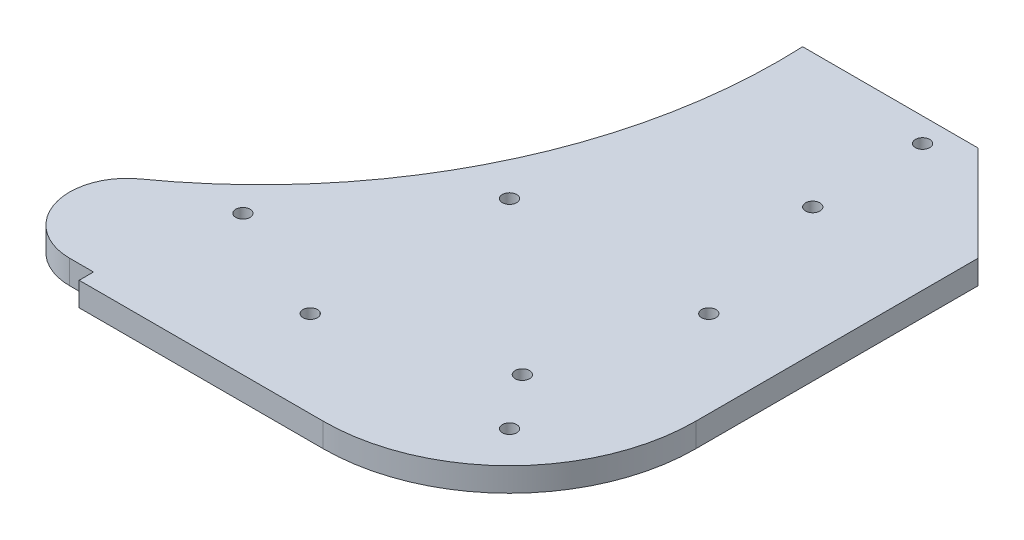
SolidWorks part; units mm, degrees
material "ABS PC"
ref_plane "Plan de face" through (0, 0, 0) normal (0, 0, 1) x (1, 0, 0)
ref_plane "Plan de dessus" through (0, 0, 0) normal (0, 1, 0) x (1, 0, 0)
ref_plane "Plan de droite" through (0, 0, 0) normal (1, 0, 0) x (0, 0, -1)
sketch "Esquisse1" plane through (0, 0, 0) normal (0, 1, 0) x (1, 0, 0)
  line L0 (-56.1, -39) -> (0, -39) construction
  line L1 (39, 0) -> (39, 164.5704) construction
  line L2 (-51.1, -39) -> (0, -39)
  line L3 (39, 0) -> (39, 59.0829)
  line L4 (-51.1, -36) -> (-51.1, -39) construction
  line L5 (-56.1, -36) -> (-51.1, -36) construction
  line L6 (-51.1, -36) -> (-51.1, -39)
  line L7 (-56.1, -36) -> (-51.1, -36)
  line L8 (-17.7153, 79.0829) -> (19, 79.0829)
  line L10 (7.4, 79.0829) -> (17.4, 79.0829) construction
  line L11 (19, 79.0829) -> (39, 59.0829)
  arc A0 (0, -39) -> (39, 0) centre (0, 0) ccw construction
  arc A2 (0, -39) -> (39, 0) centre (0, 0) ccw
  arc A3 (-63.071, -14.2324) -> (-189.129, -14.2324) centre (-126.1, 74.0829) ccw construction
  arc A4 (-63.071, -14.2324) -> (-17.7153, 79.0829) centre (-126.1, 74.0829) ccw
  arc A6 (-63.071, -14.2324) -> (-56.1, -36) centre (-56.1, -24) ccw
  arc A7 (-63.071, -14.2324) -> (-56.1, -36) centre (-56.1, -24) ccw construction
  point P13 (39, 79.0829)
extrude "Boss.-Extru.1" add sketch "Esquisse1" along normal blind 5
sketch "Esquisse2" plane through (0, 0, 0) normal (0, -1, 0) x (1, 0, 0)
  circle A0 centre (20.8597, 20.8597) radius 1.5
  circle A1 centre (20.8597, -20.8597) radius 1.5
  circle A2 centre (-20.8597, -20.8597) radius 1.5
  circle A3 centre (-20.8597, 20.8597) radius 1.5
  circle A4 centre (12.4, -74.0829) radius 1.5
  circle A5 centre (12.4, 9.7171) radius 1.5
  dimension "D1" = 3
extrude "Enlèv. mat.-Extru.1" cut sketch "Esquisse2" against normal through all
sketch "Esquisse3" plane through (0, 5, 0) normal (0, 1, 0) x (1, 0, 0)
  line L0 (12.4, 51.0829) -> (17.4, 51.0829) construction
  line L1 (-46.1, -9.7171) -> (-46.1, -14.7171) construction
  line L2 (17.4, 52.5829) -> (17.4, 49.5829) construction
  line L3 (-44.6, -14.7171) -> (-47.6, -14.7171) construction
  circle A0 centre (12.4, 51.0829) radius 1.5
  circle A1 centre (-46.1, -9.7171) radius 1.5
  dimension "D1" = 3
  dimension "D2" = 5
extrude "Enlèv. mat.-Extru.2" cut sketch "Esquisse3" against normal through all
